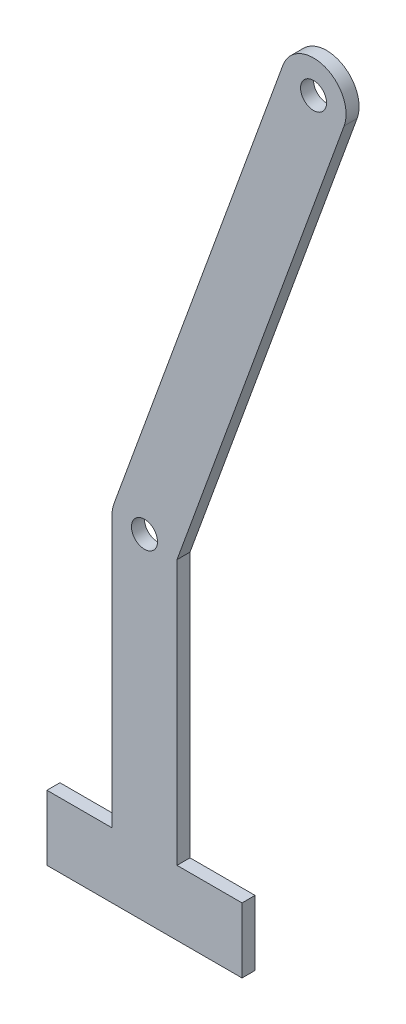
SolidWorks part; units mm, degrees
ref_plane "Front Plane" through (0, 0, 0) normal (0, 0, 1) x (1, 0, 0)
ref_plane "Top Plane" through (0, 0, 0) normal (0, 1, 0) x (1, 0, 0)
ref_plane "Right Plane" through (0, 0, 0) normal (1, 0, 0) x (0, 0, -1)
sketch "Sketch1" plane through (0, 0, 0) normal (0, 0, 1) x (1, 0, 0)
  line L0 (-76.2, 0) -> (-76.2, -95.25) construction
  line L1 (-27.94, -19.05) -> (-124.46, -19.05) construction
  line L2 (-27.94, -19.05) -> (-27.94, -171.45) construction
  line L3 (-27.94, -171.45) -> (-124.46, -171.45) construction
  line L4 (-124.46, -19.05) -> (-124.46, -171.45) construction
  line L5 (-27.94, -19.05) -> (-124.46, -171.45) construction
  line L6 (-27.94, -171.45) -> (-124.46, -19.05) construction
  line L7 (0, 0) -> (-76.2, 0) construction
  line L8 (-27.94, -19.05) -> (-60.9518, -109.7491) construction
  line L9 (-21.973, -21.2218) -> (-54.9847, -111.921)
  line L10 (-33.907, -16.8782) -> (-66.9188, -107.5773)
  line L11 (-27.94, -19.05) -> (-20.32, -19.05) construction
  line L12 (-60.9518, -19.05) -> (-60.9518, -162.56) construction
  line L13 (-67.3018, -109.7491) -> (-67.3018, -162.56)
  line L14 (-54.6018, -109.7491) -> (-54.6018, -162.56)
  line L15 (-67.3018, -162.56) -> (-80.0018, -162.56)
  line L16 (-80.0018, -162.56) -> (-80.0018, -175.26)
  line L17 (-80.0018, -175.26) -> (-41.9018, -175.26)
  line L18 (-41.9018, -175.26) -> (-41.9018, -162.56)
  line L19 (-41.9018, -162.56) -> (-54.6018, -162.56)
  circle A0 centre (-27.94, -19.05) radius 2.54
  circle A1 centre (-124.46, -19.05) radius 2.54
  circle A2 centre (-124.46, -171.45) radius 2.54
  circle A3 centre (-27.94, -171.45) radius 2.54
  circle A4 centre (-60.9518, -109.7491) radius 2.54
  circle A5 centre (-27.94, -19.05) radius 6.35
  circle A6 centre (-60.9518, -109.7491) radius 6.35
  point P30 (0, 0)
  dimension "D4" = 5.08
  dimension "D6" = 5.08
  dimension "D9" = 3.81
  dimension "D10" = 5.08
  dimension "D11" = 3.81
  dimension "D1" = 95.25
  dimension "D2" = 76.2
  dimension "D3" = 152.4
  dimension "D5" = 96.52
  dimension "D7" = 96.52
  dimension "D8" = 20
  dimension "D12" = 7.62
  dimension "D13" = 143.51
  dimension "D14" = 38.1
  dimension "D15" = 12.7
  dimension "D16" = 12.7
extrude "Boss-Extrude1" add sketch "Sketch1" along normal blind 2.54 contours A6 L9 A5 L10 | A5 A0 | A6 A4 | A6 L13 L15 L16 L17 L18 L19 L14 L9 | A6 L9 L14 region at (-44.4452, -64.3965, 0) region at (-30.0504, -24.8483, 0) region at (-60.9522, -152.0578, 0) region at (-54.6788, -110.8552, 0) region at (-62.0233, -115.8258, 0)
